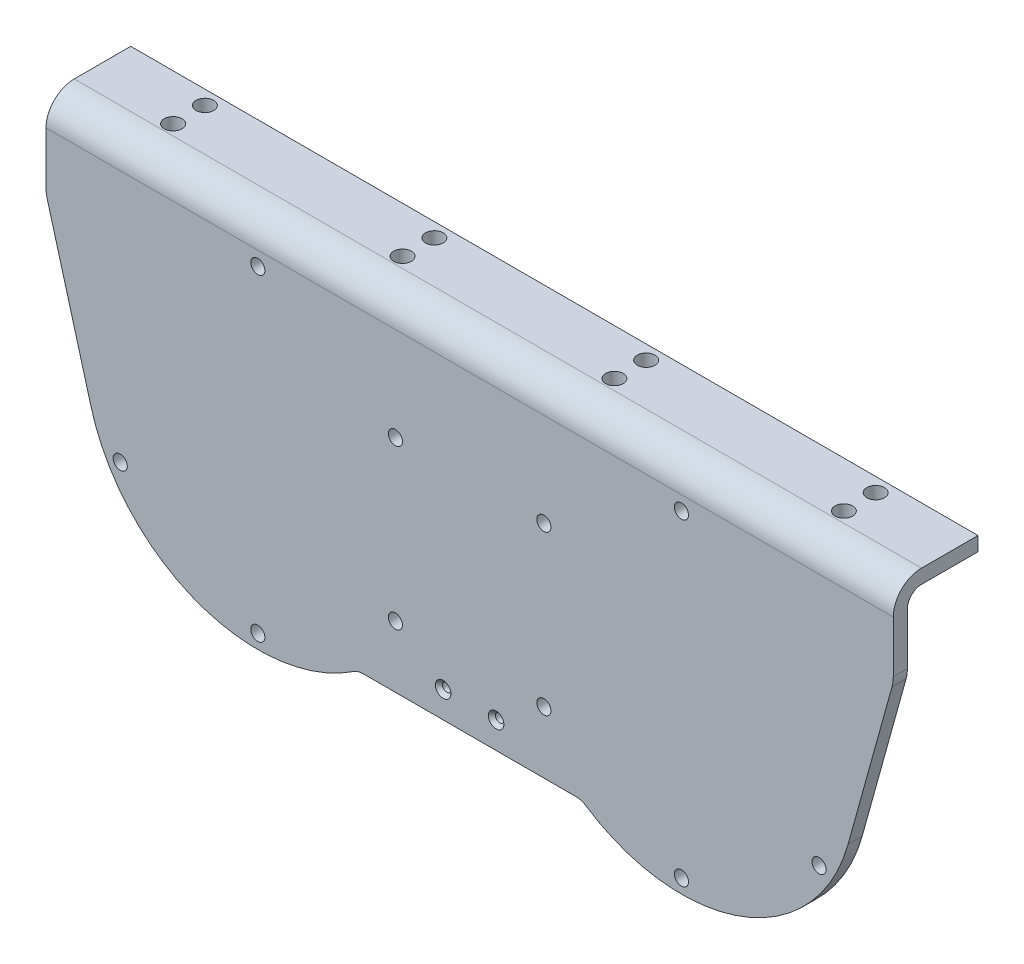
SolidWorks part; units mm, degrees
note: '?' marks a value the reader was unsure of.
material "1060 Alloy"
ref_plane "Front Plane" through (0, 0, 0) normal (0, 0, 1) x (1, 0, 0)
ref_plane "Top Plane" through (0, 0, 0) normal (0, 1, 0) x (1, 0, 0)
ref_plane "Right Plane" through (0, 0, 0) normal (1, 0, 0) x (0, 0, -1)
sketch "Sketch1" plane through (0, 0, 0) normal (0, 0, 1) x (1, 0, 0)
  line L0 (-65, 55) -> (65, 55)
  line L1 (65, 55) -> (46.8542, -14.3416)
  line L3 (55, 0) -> (-55, 0) construction
  line L4 (0, -44.7868) -> (0, 44.7868) construction
  line L5 (-65, 55) -> (-65, 51)
  line L6 (-47.2165, -13.0995) -> (-65, 51)
  arc A0 (-47.2165, -13.0995) -> (46.8542, -14.3416) centre (0, 0) ccw
  dimension "D1" = 49
  dimension "D2" = 130
  dimension "D3" = 55
  dimension "D4" = 65
  dimension "D5" = 4
extrude "Boss-Extrude1" add sketch "Sketch1" along normal blind 4
ref_plane "Plane1" through (60, 0, 0) normal (1, 0, 0) x (0, 0, -1)
ref_plane "Plane4" through (-60, 0, 0) normal (1, 0, 0) x (0, 0, -1)
ref_axis "Axis2" through (-60, 32.9778, 0) along (0, 0, 1)?
ref_axis "Axis1" through (0, 0, 54.5094) along (0, 0, -1)?
sketch "Sketch17" plane through (-60, 0, 0) normal (1, 0, 0) x (0, 0, -1)
  line L0 (20, 53) -> (20, 57)
  line L1 (20, 57) -> (4, 57)
  line L2 (-4, 49) -> (-4, 32.9778)
  line L3 (-4, 32.9778) -> (0, 32.9778)
  line L4 (0, 32.9778) -> (0, 49)
  line L5 (4, 53) -> (20, 53)
  line L6 (-4, 51) -> (-4, -13.0995) construction
  line L7 (-54.5094, 0) -> (55.4906, 0) construction
  line L9 (0, 32.9778) -> (-4, 32.9778) construction
  arc A0 (4, 57) -> (-4, 49) centre (4, 49) ccw
  arc A1 (0, 49) -> (4, 53) centre (4, 49) cw
  dimension "D5" = 8
  dimension "D6" = 4
  dimension "D1" = 24
  dimension "D2" = 4
  dimension "D3" = 4
  dimension "D4" = 0
  dimension "D7" = 57
  dimension "D8" = 0
extrude "Boss-Extrude7" add sketch "Sketch17" along normal blind 240
mirror "Mirror1" about plane through (60, 0, 0) normal (1, 0, 0) of "Boss-Extrude1"
fillet "Fillet1" [suppressed] radius 5
hole_wizard "Ø4.0mm Dowel Hole1" positions "Sketch2" profile "Sketch3" hole size "Ø4.0" standard "ISO"
sketch "Sketch2" plane through (0, 0, 4) normal (0, 0, 1) x (1, 0, 0)
  line L0 (0, -44.7868) -> (0, 44.7868) construction
  line L1 (55, 0) -> (-55, 0) construction
  point P0 (0, 45)
  dimension "D1" = 45
sketch "Sketch3" plane through (0, 45, 4) normal (1, 0, 0) x (0, -1, 0)
  line L0 (0, 0) -> (0, 51.2017)
  line L1 (0, 51.2017) -> (2, 50)
  line L2 (2, 50) -> (2, 0)
  line L5 (2, 0) -> (0, 0)
  line L10 (0, 51.2017) -> (-2, 50) construction
  line L11 (0, -6.35) -> (0, 107.95) construction
  dimension "Hole Dia." = 4
  dimension "Hole Depth" = 50
  dimension "Drill Angle" = 118
pattern_circular "CirPattern1" count 5 every 60 about axis through (0, 0, 0) along (0, 0, 1) of "Ø4.0mm Dowel Hole1"
mirror "Mirror2" about plane through (60, 0, 0) normal (1, 0, 0) of "CirPattern1", "Ø4.0mm Dowel Hole1"
sketch "Sketch4" plane through (0, 0, 0) normal (0, 0, 1) x (1, 0, 0)
  line L1 (-65, 55) -> (185, 55)
  line L2 (-65, 55) -> (-65, 51)
  line L3 (-65, 51) -> (185, 51)
  line L4 (185, 55) -> (185, 51)
extrude "Boss-Extrude2" [suppressed] add sketch "Sketch4" against normal blind 20
hole_wizard "Ø5.0mm Dowel Hole1" [suppressed] positions "Sketch5" profile "Sketch6" hole size "Ø5.0" standard "ISO"
sketch "Sketch5" [suppressed] plane through (0, 55, 0) normal (0, 1, 0) x (1, 0, 0)
  line L0 (185, 20) -> (-65, 20) construction
  line L1 (-65, -4) -> (-65, 20) construction
  point P0 (-35, 15)
  point P2 (-35, 6)
  dimension "D1" = 5
  dimension "D2" = 9
  dimension "D3" = 30
sketch "Sketch6" plane through (-35, 55, -15) normal (1, 0, 0) x (0, 0, 1)
  line L0 (0, 0) -> (0, 51.5022)
  line L1 (0, 51.5022) -> (2.5, 50)
  line L2 (2.5, 50) -> (2.5, 0)
  line L5 (2.5, 0) -> (0, 0)
  line L10 (0, 51.5022) -> (-2.5, 50) construction
  line L11 (0, -6.35) -> (0, 107.95) construction
  dimension "Hole Dia." = 5
  dimension "Hole Depth" = 50
  dimension "Drill Angle" = 118
pattern_linear "LPattern1" [suppressed] count 2 spacing 65
mirror "Mirror3" [suppressed] about plane through (60, 0, 0) normal (1, 0, 0)
ref_plane "Plane3" through (-55, 0, 0) normal (-1, 0, 0) x (0, 0, 1)
sketch "Sketch7" [suppressed] plane through (-55, 0, 0) normal (-1, 0, 0) x (0, 0, 1)
  line L0 (0, 51) -> (0, 41)
  line L1 (0, 51) -> (0, -13.0995) construction
  line L2 (0, 41) -> (-10, 51)
  line L3 (-10, 51) -> (0, 51)
  line L4 (-20, 51) -> (0, 51) construction
  dimension "D1" = 10
  dimension "D2" = 10
  dimension "D3" = 45
  dimension "D4" = 0
extrude "Boss-Extrude3" [suppressed] add sketch "Sketch7" along normal blind 5
fillet "Fillet2" [suppressed] radius 5
mirror "Mirror5" [suppressed] about plane through (60, 0, 0) normal (1, 0, 0)
sketch "Sketch8" [suppressed] plane through (60, 0, 0) normal (1, 0, 0) x (0, 0, -1)
  line L0 (0, 51) -> (0, 41)
  line L1 (0, 44.2539) -> (0, -44.2539) construction
  line L2 (0, 41) -> (10, 51)
  line L3 (20, 51) -> (0, 51) construction
  line L4 (10, 51) -> (0, 51)
  dimension "D1" = 10
extrude "Boss-Extrude4" [suppressed] add sketch "Sketch8" along normal mid plane 20
fillet "Fillet3" [suppressed] radius 5
sketch "Sketch11" plane through (0, 0, 4) normal (0, 0, 1) x (1, 0, 0)
  line L2 (28.3019, -40) -> (91.6981, -40)
  line L3 (91.6981, -40) -> (77.7491, -24.8166)
  line L4 (77.7491, -24.8166) -> (71.1104, 23.5995)
  line L5 (71.1104, 23.5995) -> (49.7127, 23.5995)
  line L6 (49.7127, 23.5995) -> (42.8102, -23.8388)
  line L7 (42.8102, -23.8388) -> (28.3019, -40)
  arc A0 (-47.2165, -13.0995) -> (46.8542, -14.3416) centre (0, 0) ccw construction
  arc A1 (73.1458, -14.3416) -> (167.2165, -13.0995) centre (120, 0) ccw construction
  dimension "D1" = 40
extrude "Boss-Extrude5" add sketch "Sketch11" against normal blind 4
fillet "Fillet4" radius 5 2 edges at (28.3019, -40, 2) (91.6981, -40, 2)
sketch "Sketch12" plane through (60, 0, 0) normal (1, 0, 0) x (0, 0, -1)
  line L0 (0, -40) -> (15, -40)
  line L5 (15, -40) -> (15, -25)
  line L6 (15, -25) -> (0, -25)
  line L7 (0, -40) -> (0, -25)
  line L8 (0, -24.5) -> (0, -20.5) construction
  dimension "D1" = 15
  dimension "D4" = 15
extrude "Boss-Extrude6" [suppressed] add sketch "Sketch12" against normal mid plane 30 separate body
hole_wizard "M5 Tapped Hole1" [suppressed] positions "Sketch13" profile "Sketch14" tap size "M5" standard "ISO"
sketch "Sketch13" [suppressed] plane through (0, -40, 0) normal (0, -1, 0) x (-1, 0, 0)
  line L0 (-60, 55.6343) -> (-60, -55.6343) construction
  line L2 (-45, 15) -> (-75, 15) construction
  point P0 (-52.5, 8.75)
  point P2 (-67.5, 8.75)
  dimension "D1" = 7.5
  dimension "D2" = 7.5
  dimension "D3" = 6.25
sketch "Sketch14" plane through (52.5, -40, -8.75) normal (1, 0, 0) x (0, 0, -1)
  line L0 (0, 0) -> (0, 13.6618)
  line L1 (0, 13.6618) -> (2.1, 12.4)
  line L2 (2.1, 12.4) -> (2.1, 0)
  line L5 (2.1, 0) -> (0, 0)
  line L10 (0, 13.6618) -> (-2.1, 12.4) construction
  line L11 (0, -6.35) -> (0, 107.95) construction
  dimension "Tap Drill Dia." = 4.2
  dimension "Tap Drill Depth" = 12.4
  dimension "Drill Angle" = 118
fillet "Fillet5" [suppressed] radius 2.5
fillet "Fillet6" [suppressed] radius 2.5
hole_wizard "CSK for M2 Countersunk Flat Head Screw1" positions "Sketch15" profile "Sketch16" countersink size "M2" standard "ISO"
sketch "Sketch15" plane through (0, 0, 4) normal (0, 0, 1) x (1, 0, 0)
  line L0 (29.8496, -40) -> (90.1504, -40) construction
  line L1 (60, -55.6343) -> (60, 55.6343) construction
  point P0 (52.5, -32.5)
  point P2 (67.5, -32.5)
  dimension "D1" = 7.5
  dimension "D2" = 15
  dimension "D3" = 0
  dimension "D4" = 7.5
sketch "Sketch16" plane through (52.5, -32.5, 4) normal (1, 0, 0) x (0, -1, 0)
  line L0 (0, 0) -> (0, 9.721)
  line L1 (0, 9.721) -> (1.2, 9)
  line L2 (1.2, 9) -> (1.2, 1)
  line L3 (1.2, 1) -> (2.2, 0)
  line L5 (2.2, 0) -> (0, 0)
  line L6 (-1.2, 1) -> (-2.2, 0) construction
  line L10 (0, 9.721) -> (-1.2, 9) construction
  line L11 (0, -6.35) -> (0, 107.95) construction
  dimension "Hole Dia." = 2.4
  dimension "Hole Depth" = 9
  dimension "Near C'Sink Dia." = 4.4
  dimension "Near C'Sink Angle" = 90
  dimension "Drill Angle" = 118
sketch "Sketch18" plane through (0, 0, 0) normal (0, 0, -1) x (-1, 0, 0)
  line L0 (60, 55) -> (60, 32.9778)
  line L1 (60, 55.6343) -> (60, -55.6343) construction
  line L3 (65, 51) -> (47.2165, -13.0995) construction
  line L4 (60, 32.9778) -> (65, 51)
  line L5 (65, 51) -> (65, 55)
  line L6 (65, 55) -> (60, 55)
extrude "Cut-Extrude1" cut sketch "Sketch18" against normal blind 4
mirror "Mirror6" about plane through (60, 0, 0) normal (1, 0, 0) of "Cut-Extrude1"
sketch "Sketch19" plane through (-60, 0, 0) normal (-1, 0, 0) x (0, 0, 1)
  line L2 (1.2915, 55) -> (4, 55)
  line L4 (4, 55) -> (4, 32.9778) construction
  line L5 (4, 49) -> (4, 55)
  arc A1 (1.2915, 55) -> (-4, 57) centre (-4, 49) ccw construction
  arc A2 (1.2915, 55) -> (4, 49) centre (-4, 49) cw
extrude "Cut-Extrude2" cut sketch "Sketch19" against normal blind 240
hole_wizard "Ø5.0mm Dowel Hole2" positions "Sketch20" profile "Sketch21" hole size "Ø5.0" standard "ISO"
sketch "Sketch20" plane through (0, 57, 0) normal (0, 1, 0) x (1, 0, 0)
  line L0 (180, -4) -> (-60, -4) construction
  line L3 (-55, 55) -> (-55, -55) construction
  point P0 (-35, 7)
  point P2 (-35, 16)
  dimension "D1" = 11
  dimension "D2" = 9
  dimension "D3" = 20
  dimension "D4" = 0
sketch "Sketch21" plane through (-35, 57, -7) normal (1, 0, 0) x (0, 0, 1)
  line L0 (0, 0) -> (0, 10.5022)
  line L1 (0, 10.5022) -> (2.5, 9)
  line L2 (2.5, 9) -> (2.5, 0)
  line L5 (2.5, 0) -> (0, 0)
  line L10 (0, 10.5022) -> (-2.5, 9) construction
  line L11 (0, -6.35) -> (0, 107.95) construction
  dimension "Hole Dia." = 5
  dimension "Hole Depth" = 9
  dimension "Drill Angle" = 118
pattern_linear "LPattern2" count 2 spacing 65 along (1, 0, 0) of "Ø5.0mm Dowel Hole2"
mirror "Mirror7" about plane through (60, 0, 0) normal (1, 0, 0) of "LPattern2", "Ø5.0mm Dowel Hole2"
fillet "Fillet7" radius 10 2 edges at (-60, 32.9778, 2) (180, 32.9778, 2)
sketch "Sketch22" plane through (0, 0, 0) normal (0, 0, -1) x (-1, 0, 0)
  line L0 (-63.2171, 23.5995) -> (-56.7829, 23.5995)
  line L1 (-63.2171, 23.5995) -> (-56.7829, 23.5995) construction
  line L2 (-56.7829, 23.5995) -> (-59.2371, 32.9778)
  line L3 (-59.2371, 32.9778) -> (-60.7629, 32.9778)
  line L4 (-60.7629, 32.9778) -> (-63.2171, 23.5995)
extrude "Boss-Extrude8" add sketch "Sketch22" against normal blind 4
equation "\"Supportwidth\"=30"
equation "\"D1@Boss-Extrude6\"=\"Supportwidth\""
equation "\"Supportlength\"=15"
equation "\"D4@Sketch12\"=\"Supportlength\""
equation "\"D1@Sketch13\"=\"Supportwidth\"/4"
equation "\"D2@Sketch13\"=\"Supportwidth\"/4"
